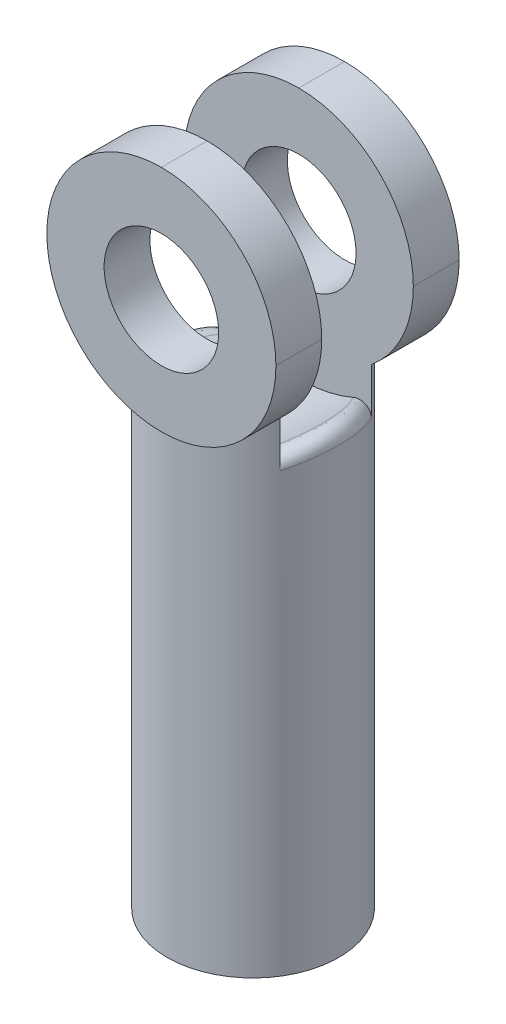
SolidWorks part; units mm, degrees
ref_plane "Front Plane" through (0, 0, 0) normal (0, 0, 1) x (1, 0, 0)
ref_plane "Top Plane" through (0, 0, 0) normal (0, 1, 0) x (1, 0, 0)
ref_plane "Right Plane" through (0, 0, 0) normal (1, 0, 0) x (0, 0, -1)
sketch "Sketch1" plane through (0, 0, 0) normal (0, 1, 0) x (1, 0, 0)
  circle A0 centre (0, 0) radius 9.525
  dimension "D1" = 19.05
extrude "Boss-Extrude1" add sketch "Sketch1" along normal blind 50.8
sketch "Sketch2" plane through (0, 50.8, 0) normal (0, 1, 0) x (1, 0, 0)
  line L1 (-12.7, -10.16) -> (12.7, -10.16)
  line L2 (-12.7, -10.16) -> (-12.7, 10.16)
  line L3 (-12.7, 10.16) -> (12.7, 10.16)
  line L4 (12.7, -10.16) -> (12.7, 10.16)
  line L5 (-12.7, -10.16) -> (12.7, 10.16) construction
  line L6 (-12.7, 10.16) -> (12.7, -10.16) construction
  point P0 (0, 0)
  dimension "D1" = 25.4
  dimension "D2" = 20.32
extrude "Boss-Extrude2" add sketch "Sketch2" along normal blind 25.4
fillet "Fillet1" radius 12.7 2 edges at (-12.7, 76.2, 0) (12.7, 76.2, 0)
fillet "Fillet2" radius 12.7 2 edges at (12.7, 50.8, 0) (-12.7, 50.8, 0)
sketch "Sketch5" plane through (0, 0, 0) normal (0, 0, 1) x (1, 0, 0)
  circle A0 centre (0, 63.5) radius 15.24
  dimension "D1" = 30.48
extrude "Cut-Extrude1" cut sketch "Sketch5" against normal mid plane 10.16
fillet "Fillet3" radius 1.27 2 edges at (9.5162, 51.5962, 0.4097) (-9.5162, 51.5962, -0.4097)
sketch "Sketch6" plane through (0, 0, 10.16) normal (0, 0, 1) x (1, 0, 0)
  circle A0 centre (0, 63.5) radius 6.35
  arc A1 (0, 76.2) -> (-12.7, 63.5) centre (0, 63.5) ccw construction
  dimension "D1" = 12.7
extrude "Cut-Extrude3" cut sketch "Sketch6" against normal through all
